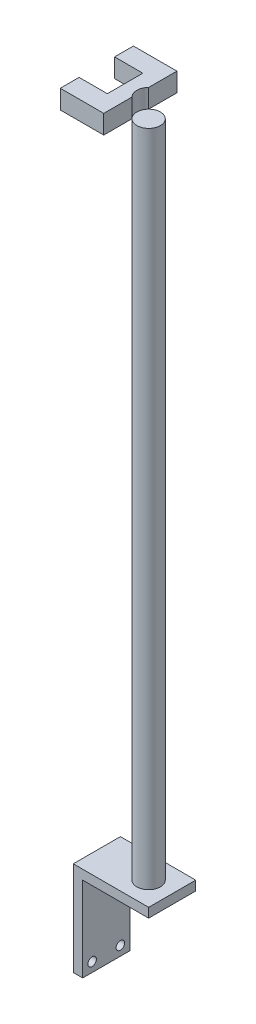
SolidWorks part; units mm, degrees
ref_plane "Płaszczyzna przednia" through (0, 0, 0) normal (0, 0, 1) x (1, 0, 0)
ref_plane "Płaszczyzna górna" through (0, 0, 0) normal (0, 1, 0) x (1, 0, 0)
ref_plane "Płaszczyzna prawa" through (0, 0, 0) normal (1, 0, 0) x (0, 0, -1)
sketch "Szkic1" plane through (0, 0, 0) normal (1, 0, 0) x (0, 0, -1)
  line L1 (0, 0) -> (50, 0)
  line L2 (0, 0) -> (0, 100)
  line L3 (0, 100) -> (50, 100)
  line L4 (50, 0) -> (50, 100)
  circle A0 centre (10, 10) radius 4.5
  circle A1 centre (40, 10) radius 4.5
  dimension "D1" = 9
  dimension "D2" = 9
  dimension "D3" = 50
  dimension "D4" = 100
  dimension "D5" = 10
  dimension "D6" = 10
  dimension "D7" = 10
  dimension "D8" = 10
extrude "Dodanie-wyciągnięcie1" add sketch "Szkic1" along normal blind 10
sketch "Szkic2" plane through (0, 0, -50) normal (0, 0, -1) x (-1, 0, 0)
  line L1 (0, 100) -> (-80, 100)
  line L2 (0, 100) -> (0, 90)
  line L3 (0, 90) -> (-80, 90)
  line L4 (-80, 100) -> (-80, 90)
  dimension "D1" = 10
  dimension "D2" = 80
extrude "Dodanie-wyciągnięcie2" add sketch "Szkic2" against normal blind 50
sketch "Szkic3" plane through (0, 100, 0) normal (0, 1, 0) x (1, 0, 0)
  line L0 (80, 0) -> (80, 50) construction
  line L1 (80, 0) -> (0, 0) construction
  circle A0 centre (55, 25) radius 12.5
  dimension "D1" = 25
  dimension "D2" = 25
  dimension "D3" = 25
extrude "Dodanie-wyciągnięcie3" add sketch "Szkic3" along normal blind 700
sketch "Szkic4" plane through (0, 800, 0) normal (0, 1, 0) x (1, 0, 0)
  line L0 (55, 25) -> (46.1612, 16.1612)
  line L9 (46.1612, 16.1612) -> (46.1612, -13.8388)
  line L10 (46.1612, -13.8388) -> (0, -13.8388)
  line L11 (0, -13.8388) -> (0, 6.1612)
  line L12 (0, 6.1612) -> (30, 6.1612)
  line L13 (30, 6.1612) -> (30, 43.8388)
  line L14 (30, 43.8388) -> (0, 43.8388)
  line L15 (0, 43.8388) -> (0, 63.8388)
  line L16 (0, 63.8388) -> (46.1612, 63.8388)
  line L17 (46.1612, 63.8388) -> (46.1612, 33.8388)
  line L18 (46.1612, 33.8388) -> (55, 25)
  circle A0 centre (55, 25) radius 12.5 construction
  circle M7 centre (55, 25) radius 12.5
  dimension "D1" = 30
  dimension "D2" = 30
  dimension "D3" = 20
  dimension "D4" = 20
  dimension "D5" = 30
extrude "Dodanie-wyciągnięcie4" add sketch "Szkic4" along normal blind 20 separate body contours L12 L10 M7 region at (45.2576, 800, -1.1612)
